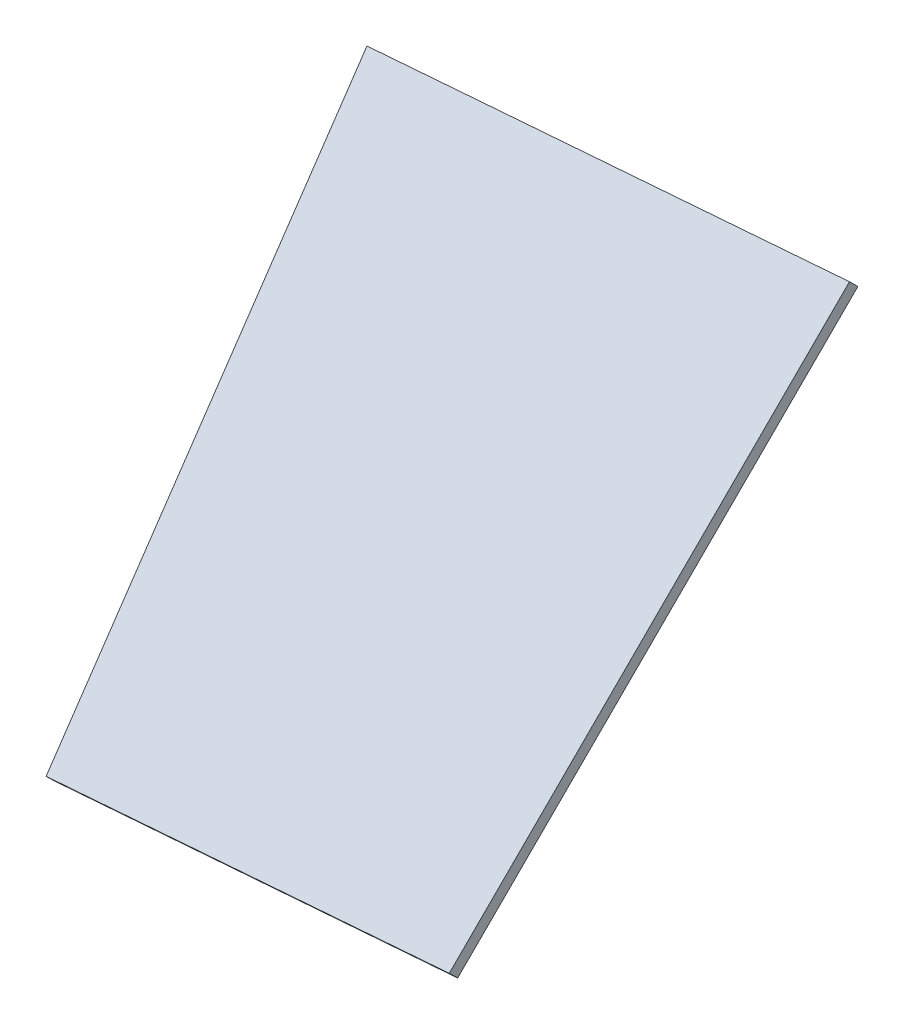
SolidWorks part; units mm, degrees
ref_plane "Front Plane" through (0, 0, 0) normal (0, 0, 1) x (1, 0, 0)
ref_plane "Top Plane" through (0, 0, 0) normal (0, 1, 0) x (1, 0, 0)
ref_plane "Right Plane" through (0, 0, 0) normal (1, 0, 0) x (0, 0, -1)
ref_plane "Pedlabox Floor Plane" through (97.6381, 1052.8823, 1069.2822) normal (-0.0649, -0.7001, -0.711) x (-0.9975, 0.0661, 0.026)
sketch "PedalBox Floor" plane through (97.6381, 1052.8823, 1069.2822) normal (-0.0649, -0.7001, -0.711) x (-0.9975, 0.0661, 0.026)
  line L0 (879.7119, -469.7168) -> (867.3237, -1020.6057)
  line L1 (867.3237, -1020.6057) -> (1228.8765, -1052.2713)
  line L2 (1228.8765, -1052.2713) -> (1312.4385, -507.616)
  line L3 (1312.4385, -507.616) -> (879.7119, -469.7168)
  line L4 (1283.0307, -505.0404) -> (909.1197, -472.2924) construction
  line L9 (1229.6836, -1047.0107) -> (1342.2348, -313.4047) construction
  line L10 (884.1292, -273.2827) -> (867.4433, -1015.2849) construction
  line L11 (1229.0175, -1052.2836) -> (867.1826, -1020.5933) construction
extrude "Boss-Extrude1" add sketch "PedalBox Floor" along normal blind 12.7 contours L3 L0 L1 L2
